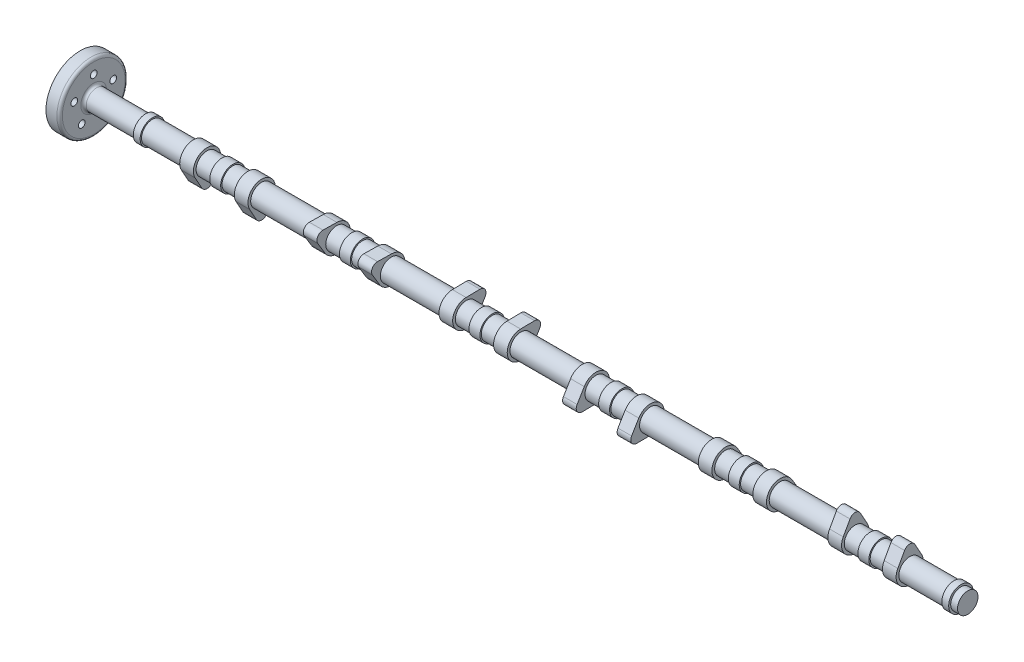
SolidWorks part; units mm, degrees
ref_plane "Front Plane" through (0, 0, 0) normal (0, 0, 1) x (1, 0, 0)
ref_plane "Top Plane" through (0, 0, 0) normal (0, 1, 0) x (1, 0, 0)
ref_plane "Right Plane" through (0, 0, 0) normal (1, 0, 0) x (0, 0, -1)
sketch "Sketch1" plane through (0, 0, 0) normal (1, 0, 0) x (0, 0, -1)
  circle A0 centre (0, 0) radius 8
  dimension "D1" = 16
extrude "Boss-Extrude1" add sketch "Sketch1" along normal mid plane 95
sketch "Sketch2" plane through (0, 0, 0) normal (1, 0, 0) x (0, 0, -1)
  line L0 (0, 0) -> (0, -16) construction
  line L1 (-8.7462, -4.8481) -> (-3.8079, -13.757)
  line L2 (8.7462, -4.8481) -> (3.8079, -13.757)
  arc A0 (-3.8079, -13.757) -> (3.8079, -13.757) centre (0, -11.6462) ccw
  circle A2 centre (0, 0) radius 10
  arc A3 (8.7462, -4.8481) -> (-8.7462, -4.8481) centre (0, 0) ccw
  dimension "D2" = 16
  dimension "D3" = 58
  dimension "D1" = 2
extrude "Boss-Extrude2" add sketch "Sketch2" along normal blind 10 from offset 15
mirror "Mirror1" about plane through (0, 0, 0) normal (1, 0, 0) of "Boss-Extrude2"
sketch "Sketch3" plane through (0, 0, 0) normal (1, 0, 0) x (0, 0, -1)
  circle A0 centre (0, 0) radius 9
  dimension "D1" = 18
extrude "Boss-Extrude3" add sketch "Sketch3" along normal mid plane 8
pattern_linear "LPattern1" count 6 spacing 95 along (1, 0, 0) of bodies 104
move or copy body "Body-Move/Copy1" bodies to move or copy 107 copy no rotation origin (0, 0, 0) rotation axis (-1, 0, 0) rotation angle 60 parameters "Angle Around Edge"=60
move or copy body "Body-Move/Copy2" bodies to move or copy 105 copy no rotation origin (0, 0, 0) rotation axis (-1, 0, 0) rotation angle 120 parameters "Angle Around Edge"=120
move or copy body "Body-Move/Copy3" bodies to move or copy 108 copy no rotation origin (0, 0, 0) rotation axis (1, 0, 0) rotation angle 60 parameters "Angle Around Edge"=300
move or copy body "Body-Move/Copy4" bodies to move or copy 106 copy no rotation origin (0, 0, 0) rotation axis (1, 0, 0) rotation angle 120 parameters "Angle Around Edge"=240
move or copy body "Body-Move/Copy5" bodies to move or copy 109 copy no rotation origin (0, 0, 0) rotation axis (1, 0, 0) rotation angle 180 parameters "Angle Around Edge"=180
sketch "Sketch4" plane through (522.5, 0, 0) normal (1, 0, 0) x (0, 0, -1)
  circle A1 centre (0, 0) radius 8
  circle A2 centre (0, 0) radius 8
  dimension "D1" = 0
extrude "Boss-Extrude4" add sketch "Sketch4" along normal blind 10
sketch "Sketch5" plane through (532.5, 0, 0) normal (1, 0, 0) x (0, 0, -1)
  circle A4 centre (0, 0) radius 9
  circle A5 centre (0, 0) radius 9
  dimension "D1" = 1
extrude "Boss-Extrude5" add sketch "Sketch5" along normal blind 5
combine bodies "Combine1" operation type add bodies to combine 104 111 113 110 112 116
sketch "Sketch6" plane through (537.5, 0, 0) normal (1, 0, 0) x (0, 0, -1)
  circle A0 centre (0, 0) radius 7.5
  dimension "D1" = 15
extrude "Boss-Extrude6" add sketch "Sketch6" along normal blind 5
sketch "Sketch7" plane through (-47.5, 0, 0) normal (-1, 0, 0) x (0, 0, 1)
  circle A1 centre (0, 0) radius 8
  circle A2 centre (0, 0) radius 8
  dimension "D1" = 0
extrude "Boss-Extrude7" add sketch "Sketch7" along normal blind 7.5
sketch "Sketch8" plane through (-55, 0, 0) normal (-1, 0, 0) x (0, 0, 1)
  circle A2 centre (0, 0) radius 9
  circle A3 centre (0, 0) radius 9
  dimension "D1" = 1
extrude "Boss-Extrude8" add sketch "Sketch8" along normal blind 5
sketch "Sketch9" plane through (-60, 0, 0) normal (-1, 0, 0) x (0, 0, 1)
  circle A0 centre (0, 0) radius 7.5
  dimension "D1" = 15
extrude "Boss-Extrude9" add sketch "Sketch9" along normal blind 38
sketch "Sketch10" plane through (-98, 0, 0) normal (-1, 0, 0) x (0, 0, 1)
  circle A0 centre (0, 0) radius 2.5
  circle A1 centre (0, 0) radius 25
  dimension "D1" = 50
  dimension "D2" = 5
extrude "Boss-Extrude10" add sketch "Sketch10" along normal blind 10
fillet "Fillet1" radius 2 2 edges at (-98, 0, 25) (-98, 0, 7.5)
sketch "Sketch11" plane through (-108, 0, 0) normal (-1, 0, 0) x (0, 0, 1)
  line L1 (0, 15) -> (-14.2658, 4.6353) construction
  line L2 (-14.2658, 4.6353) -> (-8.8168, -12.1353) construction
  line L3 (-8.8168, -12.1353) -> (8.8168, -12.1353) construction
  line L4 (8.8168, -12.1353) -> (14.2658, 4.6353) construction
  line L5 (14.2658, 4.6353) -> (0, 15) construction
  circle A0 centre (0, 0) radius 15 construction
  circle A1 centre (0, 15) radius 2.5
  circle A2 centre (-14.2658, 4.6353) radius 2.5
  circle A3 centre (-8.8168, -12.1353) radius 2.5
  circle A4 centre (8.8168, -12.1353) radius 2.5
  circle A5 centre (14.2658, 4.6353) radius 2.5
  circle A6 centre (0, 0) radius 2.5 construction
  dimension "D1" = 30
extrude "Cut-Extrude1" cut sketch "Sketch11" against normal blind 10
